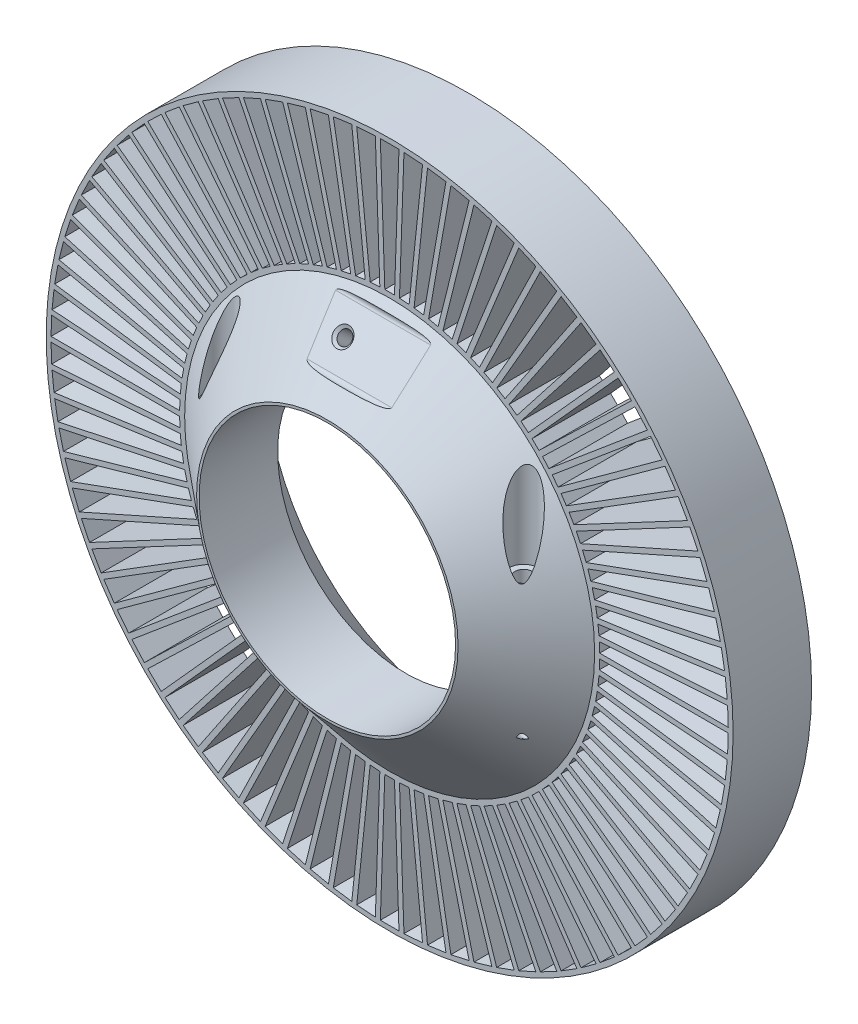
SolidWorks part; units mm, degrees
ref_plane "Front Plane" through (0, 0, 0) normal (0, 0, 1) x (1, 0, 0)
ref_plane "Top Plane" through (0, 0, 0) normal (0, 1, 0) x (1, 0, 0)
ref_plane "Right Plane" through (0, 0, 0) normal (1, 0, 0) x (0, 0, -1)
ref_axis "Axis1" through (0, 0, -18.5118) along (0, 0, 1)
sketch "Sketch1" plane through (0, 0, 0) normal (1, 0, 0) x (0, 0, -1)
  line L0 (2, 26.1366) -> (18, 26.1366)
  line L1 (18, 26.1366) -> (30.7, 41.2719)
  line L2 (30.7, 41.2719) -> (30.7, 70)
  line L3 (30.7, 70) -> (14.7, 70)
  line L4 (14.7, 70) -> (14.7, 41.7799)
  line L5 (14.7, 41.7799) -> (2, 26.6446)
  line L6 (15.412, 0) -> (45.6952, 0) construction
  line L7 (2, 26.1366) -> (2, 26.6446)
  dimension "D1" = 52.2732
  dimension "D2" = 50
  dimension "D3" = 16
  dimension "D4" = 140
  dimension "D5" = 83.5597
  dimension "D6" = 0.508
  dimension "D7" = 28.7
  dimension "D8" = 2
  dimension "D9" = 12.5832
  dimension "D10" = 0.508
revolve "Revolve1" add sketch "Sketch1" angle 360 about L6
ref_plane "Plane1" through (31, 0, 0) normal (1, 0, 0) x (0, 0, -1)
sketch "Sketch2" plane through (31, 0, 0) normal (1, 0, 0) x (0, 0, -1)
  line L0 (13.9972, 35.56) -> (13.9972, 10.0076)
  line L1 (13.9972, 10.0076) -> (12.7526, 10.0076)
  line L2 (12.7526, 10.0076) -> (12.7526, -1)
  line L3 (12.016, -18.0801) -> (11, -18.6667)
  line L4 (11, -18.6667) -> (11, 35.56)
  line L5 (11, 35.56) -> (13.9972, 35.56)
  line L6 (11, 35.56) -> (11, 47.5785) construction
  line L7 (12.7526, -1) -> (12.4478, -1.176)
  line L8 (12.4478, -1.176) -> (12.4478, -17.78)
  line L9 (2, 26.1366) -> (2, 26.6446) construction
  line L10 (12.016, -18.0801) -> (12.016, -18.0293)
  line L11 (12.016, -18.0293) -> (12.4478, -17.78)
  dimension "D1" = 5.9944
  dimension "D2" = 3.5052
  dimension "D3" = 2.8956
  dimension "D4" = 9
  dimension "D5" = 10.0076
  dimension "D6" = 1
  dimension "D7" = 2.032
  dimension "D8" = 60
  dimension "D9" = 17.78
  dimension "D10" = 0.0508
  dimension "D11" = 35.56
revolve "Cut-Revolve1" cut sketch "Sketch2" angle 360 about L6
mirror "Mirror1" about plane through (0, 0, 0) normal (1, 0, 0) of "Cut-Revolve1"
sketch "Sketch3" plane through (0, 0, 0) normal (1, 0, 0) x (0, 0, -1)
  line L0 (5.5596, 46.8678) -> (13.2342, 40.4281)
  line L1 (13.3594, 38.9968) -> (6.5022, 30.8246)
  line L2 (5.0708, 30.6994) -> (-2.6038, 37.1391)
  line L3 (-2.6038, 37.1391) -> (5.5596, 46.8678)
  line L4 (14.7, 41.7799) -> (2, 26.6446) construction
  line L5 (9.9308, 34.9107) -> (6.6967, 37.6244) construction
  arc A0 (6.5022, 30.8246) -> (5.0708, 30.6994) centre (5.7239, 31.4777) cw
  arc A1 (13.2342, 40.4281) -> (13.3594, 38.9968) centre (12.5811, 39.6498) cw
  dimension "D1" = 1.016
  dimension "D2" = 0.762
  dimension "D3" = 12.7
  dimension "D4" = 11.43
extrude "Cut-Extrude1" cut sketch "Sketch3" against normal mid plane 25.4
sketch "Sketch11" plane through (0, 9.5343, 11.3625) normal (0, 0.6428, 0.766) x (1, 0, 0)
  circle A0 centre (0, 33.1265) radius 1.016
  dimension "D1" = 2.032
extrude "Cut-Extrude5" [suppressed] cut sketch "Sketch11" against normal blind 25.4
hole_wizard "#6-32 Tapped Hole1" positions "Sketch6" profile "Sketch5" tap size "#6-32" standard "Ansi Inch" end condition through all
sketch "Sketch6" plane through (0, 9.5343, 11.3625) normal (0, 0.6428, 0.766) x (1, 0, 0)
  line L0 (-8.6306, 27.7925) -> (8.6306, 27.7925) construction
  point P0 (-4.7625, 33.1265)
  dimension "D1" = 5.334
  dimension "D2" = 4.7625
cosmetic thread "Hole Thread1" parameters "D2"=3.5052
sketch "Sketch5" plane through (-4.7625, 34.9107, -9.9308) normal (1, 0, 0) x (0, -0.766, 0.6428)
  line L0 (0, 0) -> (0, 83.3454)
  line L1 (0, 83.3454) -> (1.3525, 83.3454)
  line L2 (1.3525, 83.3454) -> (1.3525, 0.5524)
  line L3 (1.3525, 0.5524) -> (1.905, 0)
  line L5 (1.905, 0) -> (0, 0)
  line L6 (-1.3525, 0.5524) -> (-1.905, 0) construction
  line L11 (0, -6.35) -> (0, 107.95) construction
  dimension "Thru Tap Drill Dia." = 2.7051
  dimension "Thru Tap Drill Depth" = 83.3454
  dimension "Near C'Sink Dia." = 3.81
  dimension "Near C'Sink Angle" = 90
sketch "Sketch9" plane through (0, 0, -14.7) normal (0, 0, 1) x (1, 0, 0)
  line L0 (1.9007, 68.984) -> (-1.9007, 68.984)
  line L1 (1.9007, 68.984) -> (0.9862, 42.7959)
  line L2 (0.9862, 42.7959) -> (-0.9862, 42.7959)
  line L3 (-0.9862, 42.7959) -> (-1.9007, 68.984)
  line L4 (0, 77.5019) -> (0, 89.5937) construction
  line L5 (2.2024, 63.0696) -> (1.8337, 52.5099) construction
  dimension "D1" = 1.016
  dimension "D2" = 4
  dimension "D3" = 1.016
  dimension "D4" = 1.016
extrude "Cut-Extrude3" cut sketch "Sketch9" against normal up to next
pattern_circular "CirPattern1" count 90 over 360 about axis through (0, 0, -18.5118) along (0, 0, 1) of "Cut-Extrude3"
sketch "Sketch10" plane through (0, 0, 0) normal (0, 0, 1) x (1, 0, 0)
  line L1 (-96.4322, 0) -> (96.4322, 0)
  line L2 (-96.4322, 0) -> (-96.4322, -88.2501)
  line L3 (-96.4322, -88.2501) -> (96.4322, -88.2501)
  line L4 (96.4322, 0) -> (96.4322, -88.2501)
extrude "Cut-Extrude4" [suppressed] cut sketch "Sketch10" against normal through all
sketch "Sketch12" [suppressed] plane through (0, 9.5343, 11.3625) normal (0, 0.6428, 0.766) x (1, 0, 0)
  line L0 (-4.7625, 33.1265) -> (6.5405, 33.1265)
